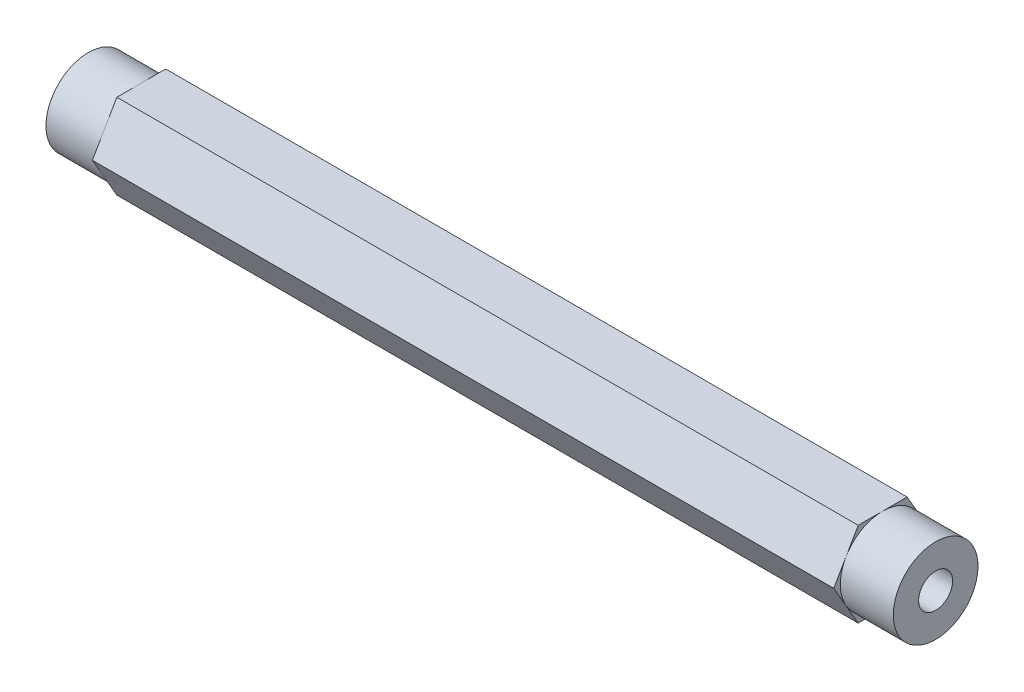
SolidWorks part; units mm, degrees
material "6061-T6 (SS)"
ref_plane "Front Plane" through (0, 0, 0) normal (0, 0, 1) x (1, 0, 0)
ref_plane "Top Plane" through (0, 0, 0) normal (0, 1, 0) x (1, 0, 0)
ref_plane "Right Plane" through (0, 0, 0) normal (1, 0, 0) x (0, 0, -1)
sketch "Sketch2" plane through (0, 0, 0) normal (1, 0, 0) x (0, 0, -1)
  line L1 (7.3323, 0) -> (3.6662, 6.35)
  line L2 (3.6662, 6.35) -> (-3.6662, 6.35)
  line L3 (-3.6662, 6.35) -> (-7.3323, 0)
  line L4 (-7.3323, 0) -> (-3.6662, -6.35)
  line L5 (-3.6662, -6.35) -> (3.6662, -6.35)
  line L6 (3.6662, -6.35) -> (7.3323, 0)
  circle A0 centre (0, 0) radius 6.35 construction
  dimension "D1" = 12.7
extrude "Boss-Extrude1" add sketch "Sketch2" along normal mid plane 127
sketch "Sketch3" plane through (63.5, 0, 0) normal (1, 0, 0) x (0, 0, -1)
  circle A0 centre (0, 0) radius 6.35
  dimension "D1" = 12.7
extrude "Cut-Extrude-Thin1" cut sketch "Sketch3" against normal blind 7.9375 thin thin type one direction wall 2.54
mirror "Mirror1" about plane through (0, 0, 0) normal (1, 0, 0) of "Cut-Extrude-Thin1"
hole_wizard "1/4-20 Tapped Hole1" positions "3DSketch1" profile "Sketch5" tap size "1/4-20" standard "ANSI Inch"
sketch3d "3DSketch1"
  line L0 (55.5625, 0, 0) -> (63.5, 0, 0) construction
  line L1 (-55.5625, 0, 0) -> (-63.5, 0, 0) construction
  point P0 (63.5, 0, 0)
  point P4 (-63.5, 0, 0)
sketch "Sketch5" plane through (63.5, 0, 0) normal (0, 1, 0) x (0, 0, -1)
  line L0 (0, 0) -> (0, 18.0438)
  line L1 (0, 18.0438) -> (2.5527, 16.51)
  line L2 (2.5527, 16.51) -> (2.5527, 0)
  line L5 (2.5527, 0) -> (0, 0)
  line L10 (0, 18.0438) -> (-2.5527, 16.51) construction
  line L11 (0, -6.35) -> (0, 107.95) construction
  dimension "Tap Drill Dia." = 5.1054
  dimension "Tap Drill Depth" = 16.51
  dimension "Drill Angle" = 118
cosmetic thread "Hole Thread1" parameters "D1"=12.7, "D2"=6.35
cosmetic thread "Hole Thread2" parameters "D1"=12.7, "D2"=6.35
